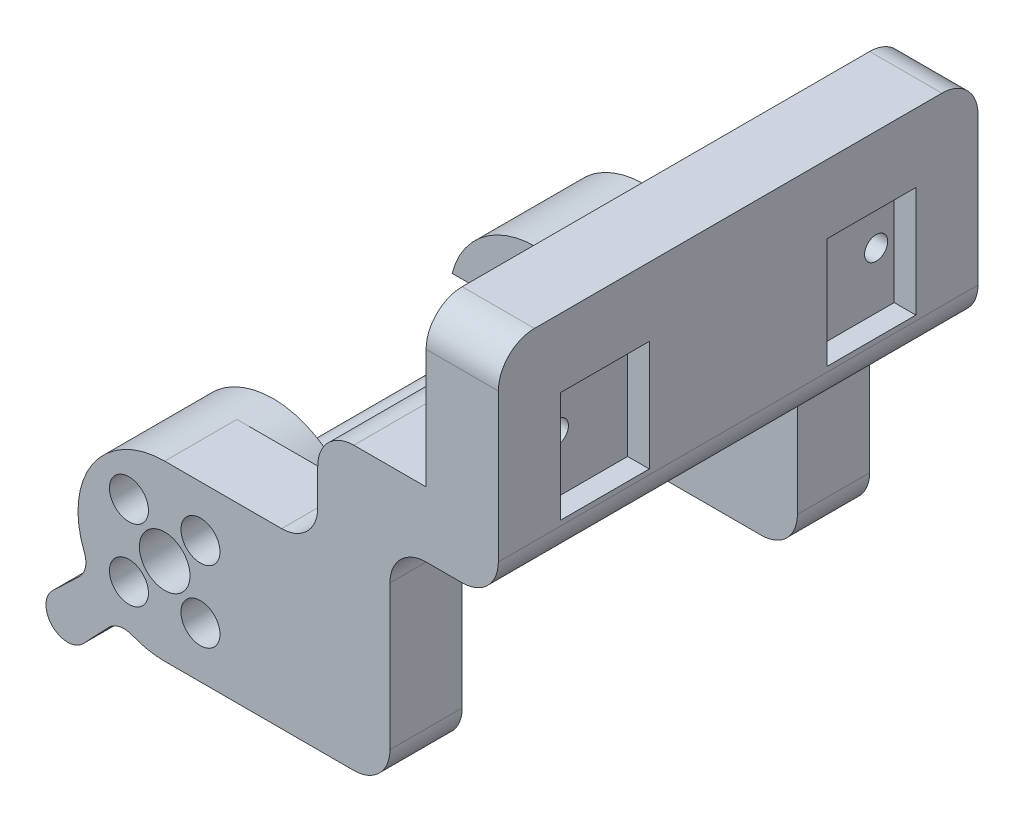
SolidWorks part; units mm, degrees
ref_plane "前视基准面" through (0, 0, 0) normal (0, 0, 1) x (1, 0, 0)
ref_plane "上视基准面" through (0, 0, 0) normal (0, 1, 0) x (1, 0, 0)
ref_plane "右视基准面" through (0, 0, 0) normal (1, 0, 0) x (0, 0, -1)
other "Configuration Table"
sketch "草图1" plane through (0, 0, 0) normal (0, 0, 1) x (1, 0, 0)
  line L0 (0, 12) -> (36.1853, 12)
  line L1 (36.1853, 12) -> (36.1853, -12)
  line L2 (36.1853, -12) -> (0, -12)
  arc A0 (0, 12) -> (0, -12) centre (0, 0) ccw
  dimension "D1" = 36.1853
extrude "凸台-拉伸1" add sketch "草图1" along normal blind 13.5
ref_plane "基准面1" through (0, 0, -16.7) normal (0, 0, -1) x (-1, 0, 0)
sketch "草图5" plane through (0, 0, 0) normal (0, 0, -1) x (-1, 0, 0)
  circle A0 centre (0, 0) radius 10.1
extrude "切除-拉伸2" cut sketch "草图5" against normal blind 1.5
sketch "草图7" plane through (0, 0, 1.5) normal (0, 0, -1) x (-1, 0, 0)
  circle A0 centre (0, 0) radius 3.5
extrude "切除-拉伸3" cut sketch "草图7" against normal blind 37
sketch "草图9" plane through (0, 0, 1.5) normal (0, 0, -1) x (-1, 0, 0)
  line L0 (-4.9497, 4.9497) -> (0, 0) construction
  line L1 (0, 0) -> (0, 7.7766) construction
  circle A0 centre (-4.9497, 4.9497) radius 1.5
  circle A1 centre (4.9497, 4.9497) radius 1.5
  circle A2 centre (4.9497, -4.9497) radius 1.5
  circle A3 centre (-4.9497, -4.9497) radius 1.5
  point P14 (0, 0)
  dimension "D1" = 7
  dimension "D2" = 45
  dimension "D3" = 4
extrude "切除-拉伸4" cut sketch "草图9" against normal blind 24.5
mirror "镜向14" about plane through (0, 0, -16.7) normal (0, 0, -1) of bodies 111
sketch "草图11" plane through (36.1853, 0, 0) normal (1, 0, 0) x (0, 0, -1)
  line L1 (-13.5, 12) -> (46.9, 12)
  line L2 (-13.5, 12) -> (-13.5, -12)
  line L3 (-13.5, -12) -> (46.9, -12)
  line L4 (46.9, 12) -> (46.9, -12)
extrude "凸台-拉伸2" add sketch "草图11" along normal blind 25
sketch "草图12" plane through (0, 0, 13.5) normal (0, 0, 1) x (1, 0, 0)
  circle A0 centre (4.9497, 4.9497) radius 2.7
  circle A1 centre (4.9497, -4.9497) radius 2.7
  circle A2 centre (-4.9497, -4.9497) radius 2.7
  circle A3 centre (-4.9497, 4.9497) radius 2.7
  point P12 (0, 0)
  dimension "D1" = 4
extrude "切除-拉伸5" cut sketch "草图12" against normal blind 8.5
sketch "草图18" plane through (0, 0, 0) normal (0, 0, -1) x (-1, 0, 0)
  circle A0 centre (0, 0) radius 12
extrude "切除-拉伸9" cut sketch "草图18" against normal blind 1.5
sketch "草图19" plane through (0, 0, 1.5) normal (0, 0, -1) x (-1, 0, 0)
  line L4 (0, 0) -> (7.3362, 0) construction
  line L5 (14.6724, -3) -> (0, -3)
  line L6 (14.6724, -3) -> (14.6724, 3)
  line L7 (14.6724, 3) -> (0, 3)
  line L8 (0, -3) -> (0, 3)
  line L9 (14.6724, -3) -> (0, 3) construction
  line L10 (14.6724, 3) -> (0, -3) construction
  point P0 (7.3362, 0)
  dimension "D1" = 6
extrude "切除-拉伸10" cut sketch "草图19" against normal blind 3
sketch "草图20" plane through (0, 0, 13.5) normal (0, 0, 1) x (1, 0, 0)
  line L1 (-17.9701, 18.7991) -> (58.5374, 18.7991)
  line L2 (-17.9701, 18.7991) -> (-17.9701, -18.303)
  line L3 (-17.9701, -18.303) -> (58.5374, -18.303)
  line L4 (58.5374, 18.7991) -> (58.5374, -18.303)
extrude "切除-拉伸11" cut sketch "草图20" against normal blind 3.5
mirror "镜向24" about plane through (0, 0, -16.7) normal (0, 0, -1) of "切除-拉伸5", "切除-拉伸9", "切除-拉伸10"
mirror "镜向26" about plane through (0, 0, -16.7) normal (0, 0, -1) of "切除-拉伸11"
sketch "草图21" plane through (0, 0, -43.4) normal (0, 0, -1) x (-1, 0, 0)
  line L0 (0, 12) -> (-61.1853, 12)
  line L1 (-61.1853, 12) -> (-61.1853, -12)
  line L2 (-61.1853, -12) -> (0, -12)
  line L3 (0, 12) -> (-58.5374, 12)
  line L5 (-58.5374, -12) -> (0, -12)
  line L13 (-58.5374, 12) -> (-58.5374, -12)
  circle A0 centre (4.9497, -4.9497) radius 2.7 construction
  arc A1 (0, -12) -> (0, 12) centre (0, 0) ccw
  arc A2 (0, -12) -> (0, 12) centre (0, 0) ccw
  circle A3 centre (0, 0) radius 3.5 construction
  circle A4 centre (4.9497, 4.9497) radius 2.7 construction
  circle A5 centre (-4.9497, 4.9497) radius 2.7 construction
  circle A6 centre (4.9497, -4.9497) radius 2.7
  circle A7 centre (0, 0) radius 3.5
  circle A8 centre (4.9497, 4.9497) radius 2.7
  circle A9 centre (-4.9497, 4.9497) radius 2.7
  circle A10 centre (-4.9497, -4.9497) radius 2.7 construction
  circle A11 centre (-4.9497, -4.9497) radius 2.7
  dimension "D1" = 0
extrude "凸台-拉伸3" add sketch "草图21" along normal blind 6.5
sketch "草图22" plane through (0, 0, -33.4) normal (0, 0, 1) x (1, 0, 0)
  line L3 (0, -12) -> (36.1853, -12)
  line L4 (36.1853, -12) -> (36.1853, 12)
  line L5 (36.1853, 12) -> (0, 12)
  line L6 (0, -12) -> (36.1853, -12)
  line L8 (36.1853, 12) -> (0, 12)
  line L9 (36.1853, -12) -> (36.1853, 12)
  arc A1 (0, -12) -> (0, 12) centre (0, 0) ccw
  arc A2 (0, -12) -> (0, 12) centre (0, 0) ccw
  dimension "D1" = 0
extrude "切除-拉伸12" cut sketch "草图22" against normal blind 6.5
mirror "镜向27" about plane through (0, 0, -16.7) normal (0, 0, -1) of "切除-拉伸12", "凸台-拉伸3"
sketch "草图23" plane through (0, 12, 0) normal (0, 1, 0) x (1, 0, 0)
  line L0 (0, 49.9) -> (61.1853, 49.9) construction
  line L1 (51.1853, 49.9) -> (61.1853, 49.9)
  line L2 (51.1853, 49.9) -> (51.1853, -16.5)
  line L3 (51.1853, -16.5) -> (61.1853, -16.5)
  line L4 (61.1853, 49.9) -> (61.1853, -16.5)
  dimension "D1" = 10
extrude "凸台-拉伸4" add sketch "草图23" along normal blind 30
sketch "草图24" plane through (0, 12, 0) normal (0, 1, 0) x (1, 0, 0)
  line L4 (51.1853, 49.9) -> (51.1853, -16.5)
  line L6 (51.1853, 49.9) -> (26.1853, 49.9)
  line L7 (0, 49.9) -> (51.1853, 49.9) construction
  line L8 (26.1853, 49.9) -> (26.1853, -16.5)
  line L9 (0, -16.5) -> (51.1853, -16.5) construction
  line L10 (26.1853, -16.5) -> (51.1853, -16.5)
  dimension "D1" = 25
extrude "凸台-拉伸5" add sketch "草图24" along normal blind 15
sketch "草图25" plane through (61.1853, 0, 0) normal (1, 0, 0) x (0, 0, -1)
  line L0 (-16.5, 42) -> (49.9, 42) construction
  line L1 (-7.9, 39) -> (4.4, 39)
  line L2 (-7.9, 39) -> (-7.9, 23.7)
  line L3 (-7.9, 23.7) -> (4.4, 23.7)
  line L4 (4.4, 39) -> (4.4, 23.7)
  line L5 (16.7, -55) -> (16.7, 55) construction
  dimension "D1" = 3
  dimension "D2" = 12.3
  dimension "D3" = 12.3
  dimension "D4" = 15.3
extrude "切除-拉伸13" cut sketch "草图25" against normal blind 3
sketch "草图26" plane through (58.1853, 0, 0) normal (1, 0, 0) x (0, 0, -1)
  line L0 (4.4, 39) -> (-7.9, 39) construction
  line L1 (-7.9, 39) -> (-7.9, 23.7) construction
  circle A0 centre (-5.4, 31.5) radius 1.6
  dimension "D1" = 7.5
  dimension "D2" = 2.5
extrude "切除-拉伸14" cut sketch "草图26" against normal blind 20
mirror "镜向28" about plane through (0, 0, -16.7) normal (0, 0, -1) of "切除-拉伸13", "切除-拉伸14"
sketch "草图27" plane through (61.1853, 0, 0) normal (1, 0, 0) x (0, 0, -1)
  line L0 (-16.5, -12) -> (49.9, -12) construction
  line L1 (-6.5, 18) -> (39.9, 18)
  line L2 (-6.5, 18) -> (-6.5, -12)
  line L3 (-6.5, -12) -> (39.9, -12)
  line L4 (39.9, 18) -> (39.9, -12)
  dimension "D1" = 0
  dimension "D2" = 0
  dimension "D3" = 30
extrude "切除-拉伸15" cut sketch "草图27" against normal blind 47
sketch "草图28" plane through (61.1853, 0, 0) normal (1, 0, 0) x (0, 0, -1)
  line L0 (-16.5, 42) -> (-16.5, -12) construction
  line L1 (-16.5, 18) -> (49.9, 18)
  line L2 (-16.5, 18) -> (-16.5, -12)
  line L3 (-16.5, -12) -> (49.9, -12)
  line L4 (49.9, 18) -> (49.9, -12)
  line L5 (39.9, 18) -> (-6.5, 18) construction
  dimension "D1" = 0
extrude "切除-拉伸16" cut sketch "草图28" against normal blind 15
sketch "草图29" plane through (0, 42, 0) normal (0, 1, 0) x (1, 0, 0)
  line L4 (51.1853, 49.9) -> (51.1853, -16.5)
  line L5 (51.1853, -16.5) -> (61.1853, -16.5)
  line L6 (61.1853, -16.5) -> (61.1853, 49.9)
  line L7 (61.1853, 49.9) -> (51.1853, 49.9)
  line L8 (51.1853, 49.9) -> (51.1853, -16.5)
  line L9 (51.1853, -16.5) -> (61.1853, -16.5)
  line L10 (61.1853, -16.5) -> (61.1853, 49.9)
  line L11 (61.1853, 49.9) -> (51.1853, 49.9)
  dimension "D1" = 0
extrude "凸台-拉伸6" add sketch "草图29" along normal blind 6.5
sketch "草图30" plane through (0, 0, 16.5) normal (0, 0, 1) x (1, 0, 0)
  line L0 (0, 0) -> (-4.9497, -4.9497) construction
  line L1 (-4.9497, -4.9497) -> (-13.435, -13.435) construction
  circle A0 centre (-13.435, -13.435) radius 3
  dimension "D2" = 6
  dimension "D1" = 12
extrude "凸台-拉伸7" add sketch "草图30" against normal up to surface (66.4 mm away) separate body
sketch "草图31" plane through (0, 0, 16.5) normal (0, 0, 1) x (1, 0, 0)
  line L0 (-13.435, -13.435) -> (-4.9497, -4.9497) construction
  line L1 (-15.5027, -11.2613) -> (-10.2272, -6.2433)
  line L2 (-6.2433, -10.2272) -> (-11.2613, -15.5027)
  circle A0 centre (-13.435, -13.435) radius 3 construction
  circle A1 centre (-4.9497, -4.9497) radius 2.7 construction
  arc A2 (-11.2613, -15.5027) -> (-15.5027, -11.2613) centre (-13.435, -13.435) ccw
  arc A4 (-10.2272, -6.2433) -> (-6.2433, -10.2272) centre (0, 0) ccw
extrude "凸台-拉伸8" add sketch "草图31" against normal up to surface (15 mm away) up to face at (0.5196, 0, 1.5)
sketch "草图32" plane through (0, 0, -49.9) normal (0, 0, -1) x (-1, 0, 0)
  line L0 (11.2613, -15.5027) -> (6.2558, -10.2404) construction
  line L1 (10.2404, -6.2558) -> (15.5027, -11.2613) construction
  line L2 (11.2613, -15.5027) -> (6.2558, -10.2404)
  line L3 (10.2404, -6.2558) -> (15.5027, -11.2613)
  arc A0 (6.2558, -10.2404) -> (10.2404, -6.2558) centre (0, 0) ccw
  circle A1 centre (13.435, -13.435) radius 3 construction
  arc A2 (15.5027, -11.2613) -> (11.2613, -15.5027) centre (13.435, -13.435) ccw
extrude "凸台-拉伸9" add sketch "草图32" against normal up to surface (15 mm away) up to face at (3.4497, -4.9497, -34.9)
fillet "圆角9" radius 3 4 edges at (-6.2558, -10.2404, 9) (-6.2558, -10.2404, -42.4) (-10.2404, -6.2558, 9) (-10.2404, -6.2558, -42.4)
sketch "草图33" plane through (26.1853, 0, 0) normal (-1, 0, 0) x (0, 0, 1)
  line L8 (-39.9, 18) -> (6.5, 18)
  line L9 (6.5, 18) -> (6.5, 12)
  line L10 (6.5, 12) -> (16.5, 12)
  line L11 (16.5, 12) -> (16.5, 27)
  line L12 (16.5, 27) -> (-49.9, 27)
  line L13 (-49.9, 27) -> (-49.9, 12)
  line L14 (-49.9, 12) -> (-39.9, 12)
  line L15 (-39.9, 12) -> (-39.9, 18)
  line L16 (-39.9, 18) -> (6.5, 18)
  line L17 (6.5, 18) -> (6.5, 12)
  line L18 (6.5, 12) -> (16.5, 12)
  line L19 (16.5, 12) -> (16.5, 27)
  line L20 (16.5, 27) -> (-49.9, 27)
  line L21 (-49.9, 27) -> (-49.9, 12)
  line L22 (-49.9, 12) -> (-39.9, 12)
  line L23 (-39.9, 12) -> (-39.9, 18)
  dimension "D1" = 0
extrude "凸台-拉伸10" add sketch "草图33" along normal blind 5
sketch "草图34" plane through (46.1853, 0, 0) normal (1, 0, 0) x (0, 0, -1)
  line L1 (-16.5, 18) -> (49.9, 18)
  line L2 (-16.5, 18) -> (-16.5, -12)
  line L3 (-16.5, -12) -> (49.9, -12)
  line L4 (49.9, 18) -> (49.9, -12)
extrude "切除-拉伸17" cut sketch "草图34" against normal blind 15
sketch "草图35" plane through (51.1853, 0, 0) normal (-1, 0, 0) x (0, 0, 1)
  line L4 (-49.9, 27) -> (16.5, 27)
  line L5 (16.5, 27) -> (16.5, 48.5)
  line L6 (16.5, 48.5) -> (-49.9, 48.5)
  line L7 (-49.9, 48.5) -> (-49.9, 27)
  line L8 (-49.9, 27) -> (16.5, 27)
  line L9 (16.5, 27) -> (16.5, 48.5)
  line L10 (16.5, 48.5) -> (-49.9, 48.5)
  line L11 (-49.9, 48.5) -> (-49.9, 27)
  circle A0 centre (5.4, 31.5) radius 1.6 construction
  circle A1 centre (-38.8, 31.5) radius 1.6 construction
  circle A2 centre (5.4, 31.5) radius 1.6
  circle A3 centre (-38.8, 31.5) radius 1.6
  dimension "D1" = 0
extrude "凸台-拉伸11" add sketch "草图35" along normal blind 15
sketch "草图36" plane through (58.1853, 0, 0) normal (1, 0, 0) x (0, 0, -1)
  line L0 (41.3, 23.7) -> (41.3, 39) construction
  line L1 (41.3, 39) -> (29, 39) construction
  line L2 (29, 39) -> (29, 23.7) construction
  line L3 (29, 23.7) -> (41.3, 23.7) construction
  line L4 (-7.9, 39) -> (-7.9, 23.7) construction
  line L5 (-7.9, 23.7) -> (4.4, 23.7) construction
  line L6 (4.4, 23.7) -> (4.4, 39) construction
  line L7 (4.4, 39) -> (-7.9, 39) construction
  line L8 (41.3, 23.7) -> (41.3, 39)
  line L9 (41.3, 39) -> (29, 39)
  line L10 (29, 39) -> (29, 23.7)
  line L11 (29, 23.7) -> (41.3, 23.7)
  line L12 (-7.9, 39) -> (-7.9, 23.7)
  line L13 (-7.9, 23.7) -> (4.4, 23.7)
  line L14 (4.4, 23.7) -> (4.4, 39)
  line L15 (4.4, 39) -> (-7.9, 39)
  circle A0 centre (38.8, 31.5) radius 1.6 construction
  circle A1 centre (-5.4, 31.5) radius 1.6 construction
  circle A2 centre (38.8, 31.5) radius 1.6
  circle A3 centre (-5.4, 31.5) radius 1.6
extrude "切除-拉伸18" cut sketch "草图36" against normal blind 15
sketch "草图37" plane through (61.1853, 0, 0) normal (1, 0, 0) x (0, 0, -1)
  line L4 (-16.5, 18) -> (49.9, 18)
  line L5 (49.9, 18) -> (49.9, 48.5)
  line L6 (49.9, 48.5) -> (-16.5, 48.5)
  line L7 (-16.5, 48.5) -> (-16.5, 18)
  line L8 (-16.5, 18) -> (49.9, 18)
  line L9 (49.9, 18) -> (49.9, 48.5)
  line L10 (49.9, 48.5) -> (-16.5, 48.5)
  line L11 (-16.5, 48.5) -> (-16.5, 18)
  dimension "D1" = 0
extrude "切除-拉伸19" cut sketch "草图37" against normal blind 15
fillet "圆角10" radius 5 9 edges at (21.1853, 12, 11.5) (21.1853, 12, -44.9) (21.1853, 27, -16.7) (31.1853, -12, -44.9) (31.1853, 18, 11.5) (31.1853, 18, -44.9) (46.1853, 18, -16.7) (41.1853, 48.5, 16.5) (41.1853, 48.5, -49.9)
fillet "圆角11" radius 5 2 edges at (28.6853, 18, -39.9) (28.6853, 18, 6.5)
